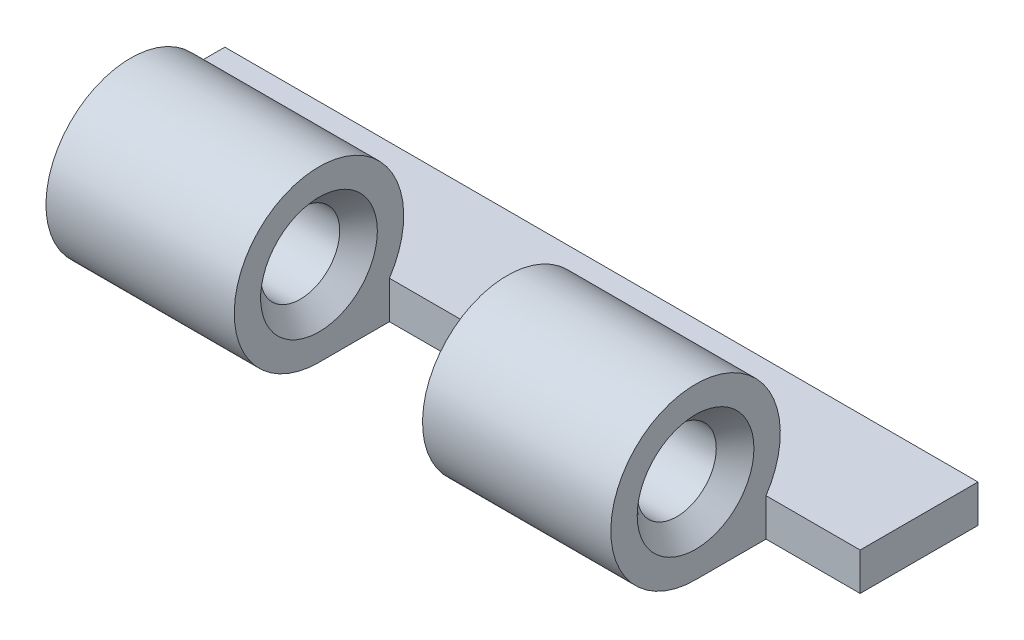
SolidWorks part; units mm, degrees
ref_plane "Ebene vorne" through (0, 0, 0) normal (0, 0, 1) x (1, 0, 0)
ref_plane "Ebene oben" through (0, 0, 0) normal (0, 1, 0) x (1, 0, 0)
ref_plane "Ebene rechts" through (0, 0, 0) normal (1, 0, 0) x (0, 0, -1)
sketch "Skizze2" plane through (0, 0, 0) normal (0, 1, 0) x (1, 0, 0)
  line L1 (-7.5, 2.5) -> (7.5, 2.5)
  line L2 (-7.5, 2.5) -> (-7.5, -2.5)
  line L3 (-7.5, -2.5) -> (7.5, -2.5)
  line L4 (7.5, 2.5) -> (7.5, -2.5)
  line L5 (-7.5, 2.5) -> (7.5, -2.5) construction
  line L6 (-7.5, -2.5) -> (7.5, 2.5) construction
  point P0 (0, 0)
  dimension "D1" = 15
  dimension "D2" = 5
extrude "Aufsatz-Linear austragen1" add sketch "Skizze2" along normal blind 1
sketch "Skizze3" plane through (7.5, 0, 0) normal (1, 0, 0) x (0, 0, -1)
  circle A0 centre (-2.5, 2.25) radius 2.25
  circle A1 centre (-2.5, 2.25) radius 1.05
  dimension "D1" = 2.1
  dimension "D2" = 4.5
extrude "Aufsatz-Linear austragen2" add sketch "Skizze3" against normal up to surface (15 mm away) up to face at (-7.5, 0.5, 0)
ref_plane "Tangential Ebene" through (0, 0, 0.25) normal (0, 0, -1) x (-1, 0, 0)
sketch "Skizze5" plane through (7.5, 0, 0) normal (1, 0, 0) x (0, 0, -1)
  line L0 (-0.6292, 1) -> (-0.6292, 0)
  line L1 (-0.6292, 0) -> (-2.5, 0)
  line L3 (2.5, 1) -> (-0.6292, 1)
  line L4 (-2.5, 0) -> (2.5, 0)
  line L5 (2.5, 0) -> (2.5, 1)
  line L6 (2.5, 1) -> (-0.6292, 1) construction
  line L7 (-2.5, 0) -> (2.5, 0) construction
  line L8 (2.5, 0) -> (2.5, 1) construction
  arc A1 (-0.6292, 1) -> (-2.5, 0) centre (-2.5, 2.25) ccw
  arc A2 (-0.6292, 1) -> (-2.5, 0) centre (-2.5, 2.25) ccw
  dimension "D1" = 0
extrude "Schnitt-Linear austragen1" cut sketch "Skizze5" against normal blind 5 from offset 5 offset against normal yes
ref_plane "Spiegelebene" through (0, 0, 0) normal (1, 0, 0) x (0, 0, -1)
sketch "Skizze7" plane through (7.5, 0, 0) normal (1, 0, 0) x (0, 0, -1)
  line L1 (-0.6292, 1) -> (2.5, 1)
  line L2 (-0.6292, 1) -> (-0.6292, 0)
  line L3 (-0.6292, 0) -> (2.5, 0)
  line L4 (2.5, 1) -> (2.5, 0)
extrude "Aufsatz-Linear austragen3" add sketch "Skizze7" along normal blind 2.5
mirror "Spiegeln1" about plane through (0, 0, 0) normal (1, 0, 0) of "Aufsatz-Linear austragen3"
chamfer "Fase1" distance 0.5 angle 45 4 edges at (-7.5, 2.25, 1.45) (-2.5, 2.25, 1.45) (2.5, 2.25, 1.45) (7.5, 2.25, 1.45)
